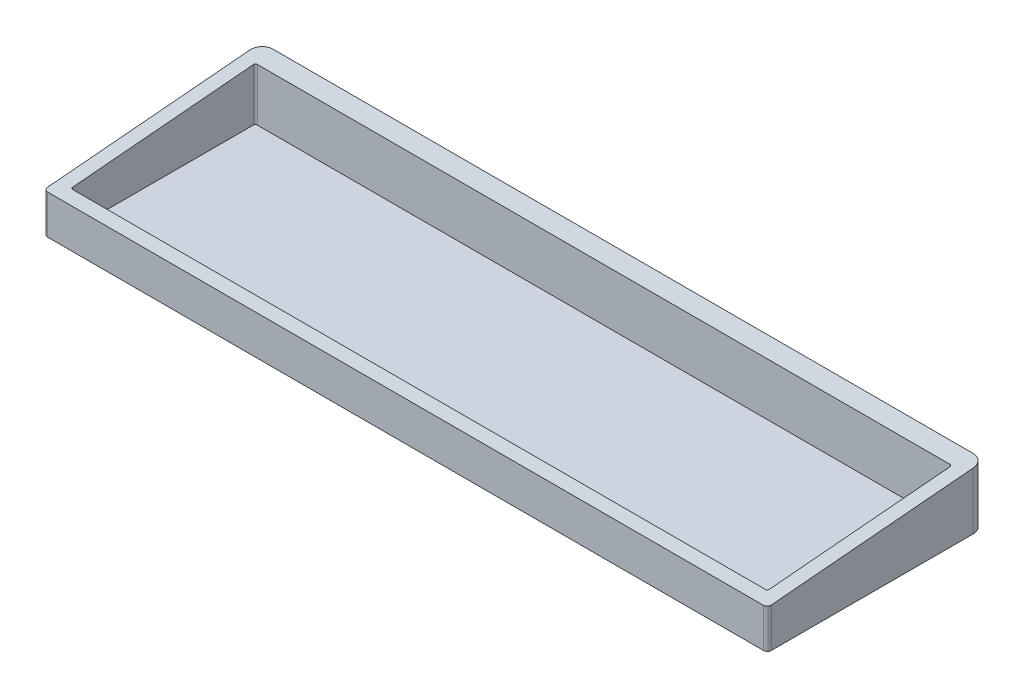
SolidWorks part; units mm, degrees
ref_plane "Front Plane" through (0, 0, 0) normal (0, 0, 1) x (1, 0, 0)
ref_plane "Top Plane" through (0, 0, 0) normal (0, 1, 0) x (1, 0, 0)
ref_plane "Right Plane" through (0, 0, 0) normal (1, 0, 0) x (0, 0, -1)
sketch "Sketch1" plane through (0, 0, 0) normal (0, 1, 0) x (1, 0, 0)
  line L1 (-178.825, 47.625) -> (178.825, 47.625)
  line L2 (-179.825, 46.625) -> (-179.825, -46.625)
  line L3 (-178.825, -47.625) -> (178.825, -47.625)
  line L4 (179.825, 46.625) -> (179.825, -46.625)
  line L5 (-179.825, 47.625) -> (179.825, -47.625) construction
  line L6 (-179.825, -47.625) -> (179.825, 47.625) construction
  arc A0 (178.825, -47.625) -> (179.825, -46.625) centre (178.825, -46.625) ccw
  arc A1 (178.825, 47.625) -> (179.825, 46.625) centre (178.825, 46.625) cw
  arc A2 (-179.825, -46.625) -> (-178.825, -47.625) centre (-178.825, -46.625) ccw
  arc A3 (-178.825, 47.625) -> (-179.825, 46.625) centre (-178.825, 46.625) ccw
  circle A4 centre (157.075, 19.175) radius 1.1
  circle A5 centre (136.925, -16.775) radius 1.1
  circle A6 centre (-153.475, 33.725) radius 1.1
  circle A7 centre (17.925, 22.275) radius 1.1
  circle A8 centre (17.875, -35.075) radius 1.1
  circle A9 centre (-130.375, -35.725) radius 1.1
  point P0 (0, 0)
  dimension "D3" = 1
  dimension "D4" = 2.2
  dimension "D7" = 2.2
  dimension "D8" = 2.2
  dimension "D9" = 2.2
  dimension "D10" = 2.2
  dimension "D11" = 2.2
  dimension "D1" = 359.65
  dimension "D2" = 95.25
  dimension "D5" = 22.75
  dimension "D6" = 28.45
  dimension "D12" = 42.9
  dimension "D13" = 30.85
  dimension "D14" = 25.35
  dimension "D15" = 161.9
  dimension "D16" = 12.55
  dimension "D17" = 161.95
  dimension "D18" = 11.9
  dimension "D19" = 49.45
  dimension "D20" = 13.9
  dimension "D21" = 26.35
sketch "Sketch2" plane through (0, 0, 0) normal (0, 1, 0) x (1, 0, 0)
  line L0 (-179.825, 46.625) -> (-179.825, -46.625) construction
  line L1 (-178.825, -47.625) -> (178.825, -47.625) construction
  line L2 (179.825, 46.625) -> (179.825, -46.625) construction
  line L3 (-178.825, 47.625) -> (178.825, 47.625) construction
  line L4 (-179.825, 46.625) -> (-179.825, -46.625)
  line L5 (-178.825, -47.625) -> (178.825, -47.625)
  line L6 (179.825, 46.625) -> (179.825, -46.625)
  line L7 (-178.825, 47.625) -> (178.825, 47.625)
  line L9 (-180.825, 57.625) -> (180.825, 57.625)
  line L10 (-186.825, 51.625) -> (-186.825, -52.625)
  line L11 (-184.825, -54.625) -> (184.825, -54.625)
  line L12 (186.825, 51.625) -> (186.825, -52.625)
  circle A0 centre (157.075, 19.175) radius 1.1 construction
  circle A1 centre (136.925, -16.775) radius 1.1 construction
  circle A2 centre (17.875, -35.075) radius 1.1 construction
  circle A3 centre (17.925, 22.275) radius 1.1 construction
  circle A4 centre (-153.475, 33.725) radius 1.1 construction
  circle A5 centre (-130.375, -35.725) radius 1.1 construction
  arc A6 (-179.825, -46.625) -> (-178.825, -47.625) centre (-178.825, -46.625) ccw construction
  arc A7 (178.825, -47.625) -> (179.825, -46.625) centre (178.825, -46.625) ccw construction
  arc A8 (179.825, 46.625) -> (178.825, 47.625) centre (178.825, 46.625) ccw construction
  arc A9 (-178.825, 47.625) -> (-179.825, 46.625) centre (-178.825, 46.625) ccw construction
  circle A10 centre (157.075, 19.175) radius 1.1
  circle A11 centre (136.925, -16.775) radius 1.1
  circle A12 centre (17.875, -35.075) radius 1.1
  circle A13 centre (17.925, 22.275) radius 1.1
  circle A14 centre (-153.475, 33.725) radius 1.1
  circle A15 centre (-130.375, -35.725) radius 1.1
  arc A16 (-179.825, -46.625) -> (-178.825, -47.625) centre (-178.825, -46.625) ccw
  arc A17 (178.825, -47.625) -> (179.825, -46.625) centre (178.825, -46.625) ccw
  arc A18 (179.825, 46.625) -> (178.825, 47.625) centre (178.825, 46.625) ccw
  arc A19 (-178.825, 47.625) -> (-179.825, 46.625) centre (-178.825, 46.625) ccw
  arc A20 (180.825, 57.625) -> (186.825, 51.625) centre (180.825, 51.625) cw
  arc A21 (-180.825, 57.625) -> (-186.825, 51.625) centre (-180.825, 51.625) ccw
  arc A22 (184.825, -54.625) -> (186.825, -52.625) centre (184.825, -52.625) ccw
  arc A23 (-186.825, -52.625) -> (-184.825, -54.625) centre (-184.825, -52.625) ccw
  point P30 (0, 0)
  dimension "D5" = 6
  dimension "D6" = 2
  dimension "D1" = 10
  dimension "D2" = 7
  dimension "D3" = 7
  dimension "D4" = 7
extrude "Boss-Extrude1" add sketch "Sketch2" along normal blind 30 contours L10 A23 L11 A22 L12 A20 L9 A21 A19 L7 A18 L6 A17 L5 A16 L4 region at (0, 0, -53.7235)
sketch "Sketch3" plane through (-186.825, 0, 0) normal (-1, 0, 0) x (0, 0, 1)
  line L0 (-57.625, 30) -> (54.625, 20.1794)
  line L1 (54.625, 30) -> (54.625, 0) construction
  line L2 (-57.625, 30) -> (-57.625, 0) construction
  line L3 (-57.625, 30) -> (54.625, 30)
  line L4 (54.625, 30) -> (54.625, 20.1794)
  dimension "D1" = 85
extrude "Cut-Extrude1" cut sketch "Sketch3" against normal blind 400
sketch "Sketch4" plane through (0, 0, 0) normal (0, -1, 0) x (1, 0, 0)
  line L4 (-179.825, 46.625) -> (-179.825, -46.625)
  line L5 (178.825, 47.625) -> (-178.825, 47.625)
  line L6 (179.825, -46.625) -> (179.825, 46.625)
  line L7 (-178.825, -47.625) -> (178.825, -47.625)
  line L8 (-179.825, 46.625) -> (-179.825, -46.625)
  line L9 (178.825, 47.625) -> (-178.825, 47.625)
  line L10 (179.825, -46.625) -> (179.825, 46.625)
  line L11 (-178.825, -47.625) -> (178.825, -47.625)
  arc A4 (-179.825, -46.625) -> (-178.825, -47.625) centre (-178.825, -46.625) ccw
  arc A5 (-178.825, 47.625) -> (-179.825, 46.625) centre (-178.825, 46.625) ccw
  arc A6 (179.825, 46.625) -> (178.825, 47.625) centre (178.825, 46.625) ccw
  arc A7 (178.825, -47.625) -> (179.825, -46.625) centre (178.825, -46.625) ccw
  arc A8 (-179.825, -46.625) -> (-178.825, -47.625) centre (-178.825, -46.625) ccw
  arc A9 (-178.825, 47.625) -> (-179.825, 46.625) centre (-178.825, 46.625) ccw
  arc A10 (179.825, 46.625) -> (178.825, 47.625) centre (178.825, 46.625) ccw
  arc A11 (178.825, -47.625) -> (179.825, -46.625) centre (178.825, -46.625) ccw
  dimension "D1" = 0
extrude "Boss-Extrude2" add sketch "Sketch4" against normal blind 2
